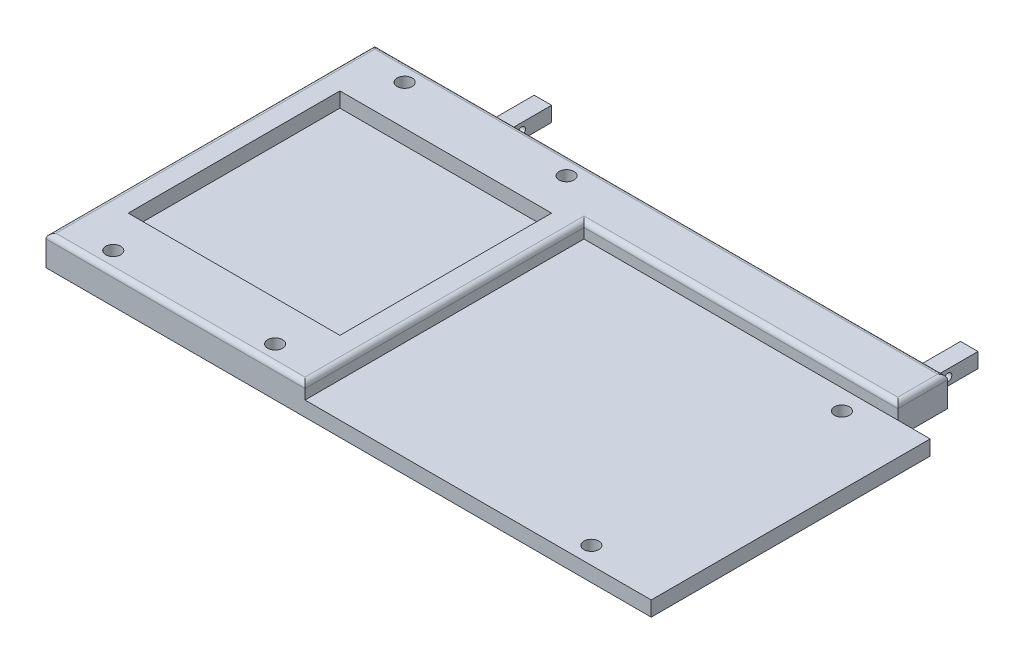
SolidWorks part; units mm, degrees
ref_plane "Front Plane" through (0, 0, 0) normal (0, 0, 1) x (1, 0, 0)
ref_plane "Top Plane" through (0, 0, 0) normal (0, 1, 0) x (1, 0, 0)
ref_plane "Right Plane" through (0, 0, 0) normal (1, 0, 0) x (0, 0, -1)
sketch "Sketch1" plane through (0, 0, 0) normal (0, 1, 0) x (1, 0, 0)
  line L1 (0, 0) -> (-52, 0)
  line L2 (0, 0) -> (0, -66)
  line L3 (0, -66) -> (-52, -66)
  line L4 (-52, 0) -> (-52, -66)
  dimension "D1" = 66
  dimension "D2" = 52
extrude "Boss-Extrude1" add sketch "Sketch1" along normal blind 6
sketch "Sketch2" plane through (0, 6, 0) normal (0, 1, 0) x (1, 0, 0)
  line L0 (-52, 0) -> (-52, -66) construction
  line L1 (-47.25, -11.75) -> (-4.75, -11.75)
  line L2 (-47.25, -11.75) -> (-47.25, -54.25)
  line L3 (-47.25, -54.25) -> (-4.75, -54.25)
  line L4 (-4.75, -11.75) -> (-4.75, -54.25)
  line L5 (-52, -66) -> (0, -66) construction
  point P6 (-47.25, -33)
  point P7 (-52, -33)
  point P8 (-26, -54.25)
  point P11 (-26, -66)
  dimension "D1" = 42.5
  dimension "D2" = 42.5
  dimension "D3" = 0
  dimension "D4" = 0
extrude "Cut-Extrude1" cut sketch "Sketch2" against normal blind 3
sketch "Sketch3" plane through (0, 6, 0) normal (0, 1, 0) x (1, 0, 0)
  line L0 (-4.75, -11.75) -> (-47.25, -11.75) construction
  line L1 (-47.25, -11.75) -> (-47.25, -54.25) construction
  line L2 (-26, 0) -> (-26, -78.9032) construction
  line L3 (0, 0) -> (-52, 0) construction
  line L4 (-52, -33) -> (19.2006, -33) construction
  line L5 (-52, 0) -> (-52, -66) construction
  circle A0 centre (-42.25, -3.75) radius 1.5
  circle A1 centre (-9.75, -3.75) radius 1.5
  circle A2 centre (-9.75, -62.25) radius 1.5
  circle A3 centre (-42.25, -62.25) radius 1.5
  dimension "D1" = 8
  dimension "D2" = 3
  dimension "D3" = 5
extrude "Cut-Extrude2" cut sketch "Sketch3" against normal blind 13
sketch "Sketch4" plane through (0, 0, 0) normal (1, 0, 0) x (0, 0, -1)
  line L0 (-66, 6) -> (0, 6) construction
  line L1 (0, 0) -> (-10, 0)
  line L2 (0, 0) -> (0, 6)
  line L3 (0, 6) -> (-10, 6)
  line L4 (-10, 0) -> (-10, 6)
  dimension "D1" = 10
extrude "Boss-Extrude2" add sketch "Sketch4" along normal blind 63
sketch "Sketch5" plane through (0, 0, 0) normal (0, 0, -1) x (-1, 0, 0)
  line L1 (30, 3) -> (26.5, 3)
  line L2 (30, 3) -> (30, 0)
  line L3 (30, 0) -> (26.5, 0)
  line L4 (26.5, 3) -> (26.5, 0)
  line L5 (-63, 0) -> (52, 0) construction
  line L6 (52, 6) -> (52, 0) construction
  line L8 (-55.6, 3) -> (-59.1, 3)
  line L9 (-55.6, 3) -> (-55.6, 0)
  line L10 (-55.6, 0) -> (-59.1, 0)
  line L11 (-59.1, 3) -> (-59.1, 0)
  point P14 (-57.35, 0)
  point P15 (28.25, 0)
  dimension "D1" = 3.5
  dimension "D2" = 22
  dimension "D3" = 3.5
  dimension "D4" = 85.6
  dimension "D5" = 3
  dimension "D6" = 90
  dimension "D7" = 3
  dimension "D8" = 90
extrude "Boss-Extrude3" add sketch "Sketch5" along normal blind 10
sketch "Sketch6" plane through (59.1, 0, 0) normal (1, 0, 0) x (0, 0, -1)
  line L0 (10, 0) -> (0, 0) construction
  line L1 (0, 3) -> (0, 0) construction
  circle A0 centre (4, 1.5) radius 0.75
  dimension "D1" = 1.5
  dimension "D2" = 4
  dimension "D3" = 1.5
extrude "Cut-Extrude3" cut sketch "Sketch6" against normal blind 114
sketch "Sketch7" plane through (0, 0, 0) normal (0, -1, 0) x (-1, 0, 0)
  line L0 (52, -66) -> (0, -66) construction
  line L1 (0, -10) -> (-69.5, -10)
  line L2 (0, -10) -> (0, -66)
  line L3 (0, -66) -> (-69.5, -66)
  line L4 (-69.5, -10) -> (-69.5, -66)
  circle A2 centre (-55.8, -14.018) radius 1.5
  circle A4 centre (-54, -62.518) radius 1.5
  dimension "D3" = 56
  dimension "D4" = 15.5
  dimension "D5" = 13.7
  dimension "D6" = 3
  dimension "D7" = 48.5
  dimension "D8" = 3
  dimension "D1" = 0
  dimension "D2" = 69.5
extrude "Boss-Extrude4" add sketch "Sketch7" against normal blind 3
fillet "Fillet1" radius 1 6 edges at (63, 6, 5) (31.5, 6, 10) (0, 6, 38) (-26, 6, 66) (-52, 6, 33) (5.5, 6, 0)
